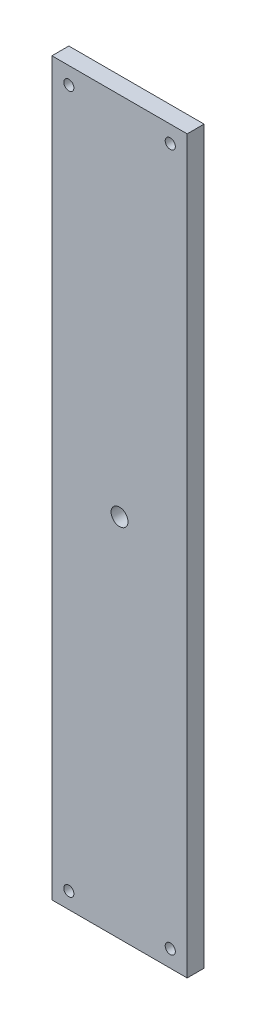
SolidWorks part; units mm, degrees
ref_plane "Front Plane" through (0, 0, 0) normal (0, 0, 1) x (1, 0, 0)
ref_plane "Top Plane" through (0, 0, 0) normal (0, 1, 0) x (1, 0, 0)
ref_plane "Right Plane" through (0, 0, 0) normal (1, 0, 0) x (0, 0, -1)
sketch "Sketch1" plane through (0, 0, 0) normal (0, 0, 1) x (1, 0, 0)
  line L1 (0, 0) -> (50.8, 0)
  line L2 (0, 0) -> (0, 274.6)
  line L3 (0, 274.6) -> (50.8, 274.6)
  line L4 (50.8, 0) -> (50.8, 274.6)
  dimension "D1" = 50.8
  dimension "D2" = 274.6
extrude "Extrude1" add sketch "Sketch1" along normal blind 6.35
hole_wizard "#10-24 Tapped Hole1" positions "3DSketch1" profile "Sketch2" tap size "#10-24" standard "Ansi Inch" end condition up to next
sketch3d "3DSketch1"
  line L0 (0, 0, 6.35) -> (50.8, 0, 6.35) construction
  line L1 (50.8, 274.6, 6.35) -> (0, 274.6, 6.35) construction
  line L2 (0, 274.6, 6.35) -> (0, 0, 6.35) construction
  point P0 (6.35, 6.096, 6.35)
  point P2 (44.4492, 6.35, 6.35)
  point P4 (44.45, 268.25, 6.35)
  point P6 (6.35, 268.25, 6.35)
  dimension "D1" = 6.096
  dimension "D2" = 6.35
  dimension "D3" = 6.35
  dimension "D4" = 6.35
  dimension "D5" = 38.1
  dimension "D6" = 38.1
  dimension "D7" = 6.35
  dimension "D8" = 6.35
sketch "Sketch2" plane through (6.35, 6.096, 6.35) normal (1, 0, 0) x (0, -1, 0)
  line L0 (0, 0) -> (0, 6.35)
  line L1 (0, 6.35) -> (1.8986, 6.35)
  line L2 (1.8986, 6.35) -> (1.8986, 0)
  line L5 (1.8986, 0) -> (0, 0)
  line L11 (0, -6.35) -> (0, 107.95) construction
  dimension "Thread Major Dia." = 3.7973
  dimension "Thru Tap Drill Depth" = 6.35
sketch "Sketch3" plane through (0, 0, 6.35) normal (0, 0, 1) x (1, 0, 0)
  line L0 (0, 0) -> (50.8, 274.6) construction
  circle A0 centre (25.4, 137.3) radius 3.175
  dimension "D1" = 6.35
extrude "Extrude2" cut sketch "Sketch3" against normal up to next
